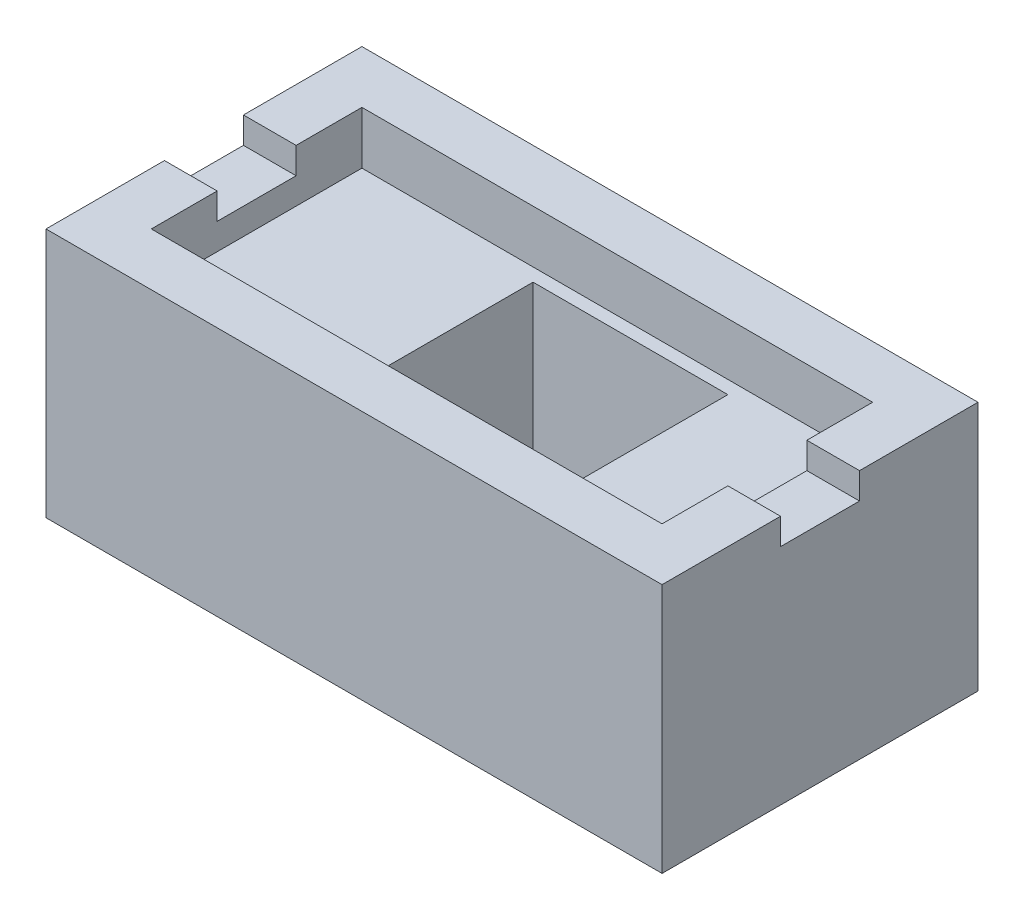
SolidWorks part; units mm, degrees
ref_plane "前视基准面" through (0, 0, 0) normal (0, 0, 1) x (1, 0, 0)
ref_plane "上视基准面" through (0, 0, 0) normal (0, 1, 0) x (1, 0, 0)
ref_plane "右视基准面" through (0, 0, 0) normal (1, 0, 0) x (0, 0, -1)
other "Configuration Table"
sketch "草图1" plane through (0, 0, 0) normal (0, 1, 0) x (1, 0, 0)
  line L0 (0, -6) -> (23.4, -6) construction
  line L1 (0, 0) -> (23.4, 0)
  line L2 (0, 0) -> (0, -12)
  line L3 (0, -12) -> (23.4, -12)
  line L4 (23.4, 0) -> (23.4, -12)
  line L5 (9, -2.5) -> (16.4, -2.5)
  line L6 (9, -2.5) -> (9, -9.5)
  line L7 (9, -9.5) -> (16.4, -9.5)
  line L8 (16.4, -2.5) -> (16.4, -9.5)
  line L10 (0, -4.5) -> (23.4, -4.5)
  line L11 (0, -4.5) -> (0, -7.5)
  line L12 (0, -7.5) -> (23.4, -7.5)
  line L13 (23.4, -4.5) -> (23.4, -7.5)
  point P11 (9, -6)
  point P16 (23.4, -6)
  dimension "D1" = 12
  dimension "D2" = 23.4
  dimension "D3" = 7
  dimension "D4" = 9
  dimension "D5" = 7
  dimension "D6" = 3
extrude "凸台-拉伸1" add sketch "草图1" along normal blind 9.5 contours L4 L3 L2 L1 | L8 L7 L6 L5
extrude "切除-拉伸2" cut sketch "草图1<4>" against normal blind 1 from surface contours L10 L13 L12 L11 starting at face at (12.7, 9.5, 6)
sketch "草图1<4>" plane through (0, 0, 0) normal (0, 1, 0) x (1, 0, 0) same geometry as "草图1"
sketch "草图2" plane through (0, 9.5, 0) normal (0, 1, 0) x (1, 0, 0)
  line L0 (0, 0) -> (23.4, 0) construction
  line L1 (2, -2) -> (21.4, -2)
  line L2 (2, -2) -> (2, -10)
  line L3 (2, -10) -> (21.4, -10)
  line L4 (21.4, -2) -> (21.4, -10)
  line L5 (0, -12) -> (23.4, -12) construction
  line L6 (0, 0) -> (0, -4.5) construction
  line L7 (23.4, 0) -> (23.4, -4.5) construction
  dimension "D1" = 2
  dimension "D2" = 2
  dimension "D3" = 2
  dimension "D4" = 2
extrude "切除-拉伸3" cut sketch "草图2" against normal blind 2
